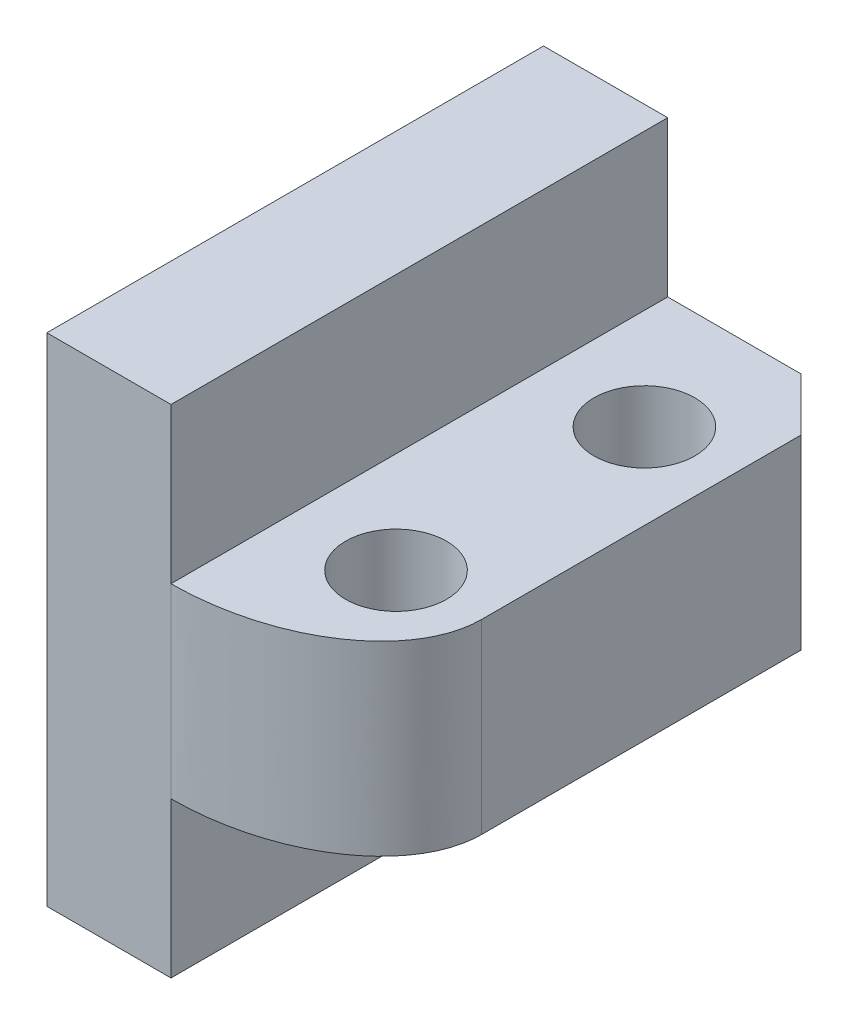
SolidWorks part; units mm, degrees
ref_plane "Front Plane" through (0, 0, 0) normal (0, 0, 1) x (1, 0, 0)
ref_plane "Top Plane" through (0, 0, 0) normal (0, 1, 0) x (1, 0, 0)
ref_plane "Right Plane" through (0, 0, 0) normal (1, 0, 0) x (0, 0, -1)
sketch "Sketch1" plane through (0, 0, 0) normal (0, 0, 1) x (1, 0, 0)
  line L0 (-4, -8) -> (-4, 8)
  line L1 (-4, 8) -> (0, 8)
  line L2 (0, 8) -> (0, 3)
  line L3 (0, 3) -> (6, 3)
  line L4 (6, 3) -> (6, -3)
  line L5 (6, -3) -> (0, -3)
  line L6 (0, -3) -> (0, -8)
  line L7 (0, -8) -> (-4, -8)
  point P10 (6, 0)
  dimension "D1" = 6
  dimension "D2" = 6
  dimension "D3" = 4
  dimension "D4" = 16
extrude "Boss-Extrude1" add sketch "Sketch1" along normal blind 16
sketch "Sketch2" plane through (0, -3, 0) normal (0, -1, 0) x (1, 0, 0)
  line L0 (0, 16) -> (0, 16.7031) construction
  line L1 (3.25, 12) -> (3.25, 16) construction
  line L2 (3.25, 4) -> (3.25, 0) construction
  line L4 (0, 16.7031) -> (6, 16.7031) construction
  line L5 (6, 16.7031) -> (6, 16) construction
  line L6 (0, 16.3516) -> (3.25, 16.3516) construction
  line L7 (3.25, 16.3516) -> (6, 16.3516) construction
  line L8 (3, 16.7031) -> (3, 16) construction
  line L9 (0, 16) -> (6, 16) construction
  line L10 (0, 0) -> (6, 0) construction
  line L11 (3.25, 16.3516) -> (3.25, 16) construction
  circle A0 centre (3.25, 12) radius 1.625
  circle A1 centre (3.25, 4) radius 1.625
  dimension "D2" = 3.25
  dimension "D1" = 4
  dimension "D3" = 0.25
extrude "Cut-Extrude1" cut sketch "Sketch2" against normal through all
chamfer "Chamfer1" distance 1.7 angle 45 1 edges at (6, 0, 0)
fillet "Fillet1" radius 4 1 edges at (6, 0, 16) second distance 6 first distance on face at (6, 0, 8.85)
